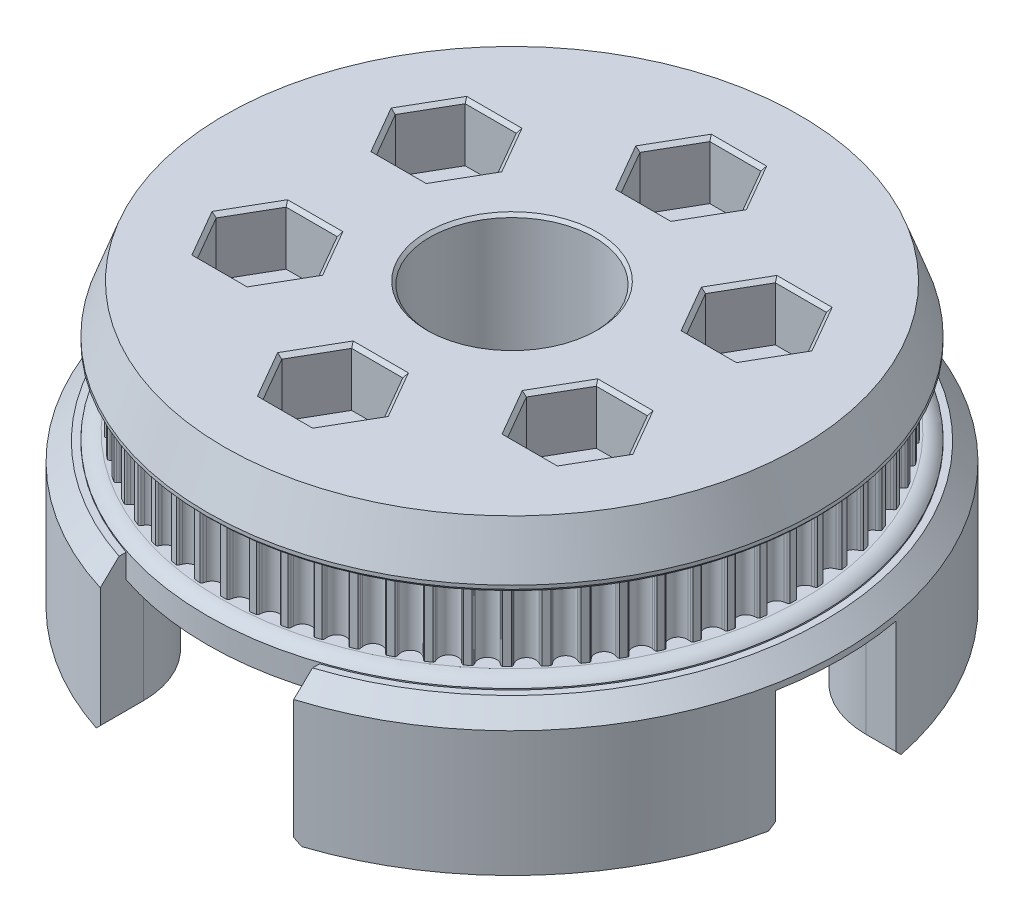
SolidWorks part; units mm, degrees
other "DetailItem2"
material "Markforged"
ref_plane "Front Plane" through (0, 0, 0) normal (0, 0, 1) x (1, 0, 0)
ref_plane "Top Plane" through (0, 0, 0) normal (0, 1, 0) x (1, 0, 0)
ref_plane "Right Plane" through (0, 0, 0) normal (1, 0, 0) x (0, 0, -1)
ref_axis "Centerline" through (0, 10.668, 0) along (0, -1, 0)
sketch "Sketch1" plane through (0, 0, 0) normal (0, 1, 0) x (1, 0, 0)
  circle A0 centre (0, 0) radius 30.6542
  dimension "OuterDiameter" = 61.3084
extrude "ToothOD" add sketch "Sketch1" along normal mid plane 7.62
sketch "Sketch2" plane through (0, 3.81, 0) normal (0, 1, 0) x (1, 0, 0)
  line L0 (0, 29.4858) -> (50000, 29.4858) construction
  line L1 (0, 30.6542) -> (50000, 30.6542) construction
  line L2 (0, 0) -> (0, 50000) construction
  arc A0 (-0.937, 30.2043) -> (0, 29.4858) centre (0, 30.4561) ccw
  arc A1 (-1.1481, 30.6327) -> (1.1481, 30.6327) centre (0, 0) cw
  circle A2 centre (0, 0) radius 30.6542 construction
  arc A3 (-0.937, 30.2043) -> (-1.0078, 30.4561) centre (-11.9754, 27.2378) ccw
  arc A4 (-1.0078, 30.4561) -> (-1.1481, 30.6327) centre (-1.2954, 30.3717) ccw
  circle A5 centre (0, 0) radius 30.6542 construction
  arc A6 (0.937, 30.2043) -> (1.0078, 30.4561) centre (11.9754, 27.2378) cw
  arc A7 (1.0078, 30.4561) -> (1.1481, 30.6327) centre (1.2954, 30.3717) cw
  arc A8 (0, 29.4858) -> (0.937, 30.2043) centre (0, 30.4561) ccw
  dimension "D1" = 1.9406
  dimension "D3" = 22.86
  dimension "D4" = 0.5994
  dimension "D2" = 1.1684
  dimension "D5" = 1.2954
extrude "ToothProfile" cut sketch "Sketch2" against normal through all
pattern_circular "ToothPattern" count 65 over 360 about axis through (0, 3.81, 0) along (0, -1, 0) of "ToothProfile"
sketch "Sketch4" plane through (0, 0, 0) normal (0, 0, 1) x (1, 0, 0)
  line L0 (0, -3.81) -> (30.9082, -3.81)
  line L1 (0, -5.08) -> (32.4322, -5.08)
  line L2 (0, -5.08) -> (0, -3.81)
  line L3 (32.4322, -5.08) -> (32.4322, -4.572)
  line L4 (0, 0) -> (50000, 0) construction
  line L5 (32.4322, 5.08) -> (32.4322, 4.572)
  line L6 (0, 5.08) -> (0, 3.81)
  line L7 (0, 5.08) -> (32.4322, 5.08)
  line L8 (0, 3.81) -> (30.9082, 3.81)
  line L9 (6.7226, -3.81) -> (6.8405, -3.81) construction
  arc A2 (30.9082, -3.81) -> (32.4322, -4.572) centre (30.9082, -5.715) cw
  arc A3 (30.9082, 3.81) -> (32.4322, 4.572) centre (30.9082, 5.715) ccw
  dimension "FlangeID" = 30.9082
  dimension "FlangeOD" = 32.4322
  dimension "D1" = 1.27
  dimension "D2" = 0.508
  dimension "D3" = 1.27
revolve "Flange" add sketch "Sketch4" angle 360 about axis through (0, 10.668, 0) along (0, -1, 0)
sketch "Sketch11" plane through (0, 5.08, 0) normal (0, 1, 0) x (1, 0, 0)
  line L0 (-3.175, 8.636) -> (3.175, 8.636) construction
  text T0 "65" font "Century Gothic" height 1.524
  point P2 (0, 8.636)
  dimension "D1" = 6.35
  dimension "D2" = 8.636
extrude "Small Tooth Count" [suppressed] cut sketch "Sketch11" against normal blind 0.4
sketch "Sketch14" plane through (0, 5.08, 0) normal (0, 1, 0) x (1, 0, 0)
  circle A0 centre (0, 0) radius 32.4322 construction
  circle A1 centre (0, 0) radius 32.4322
extrude "Boss-Extrude2" add sketch "Sketch14" along normal blind 5.842
sketch "Sketch13" plane through (0, -5.08, 0) normal (0, -1, 0) x (1, 0, 0)
  circle A0 centre (0, 0) radius 32.4322 construction
  circle A1 centre (0, 0) radius 32.4322
extrude "Boss-Extrude1" add sketch "Sketch13" along normal offset from surface (2.159 mm away) 18.161 up to face at (0, 10.922, 32.4322)
sketch "Sketch15" plane through (0, -7.239, 0) normal (0, -1, 0) x (1, 0, 0)
  line L0 (-10.287, 23.3625) -> (-10.287, 30.7575)
  line L1 (-10.287, -30.7575) -> (-10.287, -23.3625)
  arc A0 (-10.287, 23.3625) -> (-10.287, -23.3625) centre (0, 0) ccw
  arc A1 (-10.287, -30.7575) -> (-10.287, 30.7575) centre (0, 0) cw
  circle A2 centre (0, 0) radius 32.4322 construction
  dimension "D1" = 25.527
  dimension "D2" = 10.287
extrude "Boss-Extrude3" add sketch "Sketch15" along normal blind 12.7
sketch "Sketch20" plane through (0, -19.939, 0) normal (0, -1, 0) x (1, 0, 0)
  line L0 (-10.287, 33.5085) -> (-10.287, 30.7575)
  line L1 (-10.287, -33.5085) -> (-10.287, -30.7575)
  arc A0 (-10.287, -33.5085) -> (-10.287, 33.5085) centre (0, 0) cw
  arc A1 (-10.287, 30.7575) -> (-10.287, -30.7575) centre (0, 0) ccw construction
  arc A2 (-10.287, 30.7575) -> (-10.287, -30.7575) centre (0, 0) ccw
  arc A3 (-10.287, 23.3625) -> (-10.287, -23.3625) centre (0, 0) ccw construction
  dimension "D1" = 9.525
extrude "Boss-Extrude5" add sketch "Sketch20" against normal offset from surface (15.24 mm away) 2.54 up to face at (-3.4172, -7.239, 0) offset beyond the face yes
mirror "Mirror1" about plane through (0, 0, 0) normal (1, 0, 0) of "Boss-Extrude5", "Boss-Extrude3"
sketch "Sketch16" plane through (0, -7.239, 0) normal (0, -1, 0) x (1, 0, 0)
  line L0 (0, 0) -> (0, 19.05) construction
  circle A0 centre (0, 19.05) radius 2.5527
  dimension "D2" = 5.1054
  dimension "D1" = 19.05
extrude "Cut-Extrude1" cut sketch "Sketch16" against normal through all
pattern_circular "CirPattern1" count 6 over 360 about axis through (0, 10.668, 0) along (0, 1, 0) of "Cut-Extrude1"
sketch "Sketch17" plane through (0, -7.239, 0) normal (0, -1, 0) x (1, 0, 0)
  circle A0 centre (0, 0) radius 8.7376
  dimension "D1" = 17.4752
extrude "Cut-Extrude2" cut sketch "Sketch17" against normal through all
sketch "Sketch18" plane through (0, -7.239, 0) normal (0, -1, 0) x (1, 0, 0)
  circle A0 centre (0, 0) radius 12.7
  circle A1 centre (0, 0) radius 8.7376 construction
  circle A2 centre (0, 0) radius 8.7376
  dimension "D1" = 25.4
extrude "Boss-Extrude4" add sketch "Sketch18" along normal offset from surface (8.255 mm away) 15.494 up to plane "Top Plane" offset beyond the face yes
sketch "Sketch19" plane through (0, 10.922, 0) normal (0, 1, 0) x (1, 0, 0)
  line L1 (2.7203, 14.3383) -> (5.4406, 19.05)
  line L2 (5.4406, 19.05) -> (2.7203, 23.7617)
  line L3 (2.7203, 23.7617) -> (-2.7203, 23.7617)
  line L4 (-2.7203, 23.7617) -> (-5.4406, 19.05)
  line L5 (-5.4406, 19.05) -> (-2.7203, 14.3383)
  line L6 (-2.7203, 14.3383) -> (2.7203, 14.3383)
  circle A0 centre (0, 19.05) radius 4.7117 construction
  dimension "D1" = 9.4234
extrude "Cut-Extrude3" cut sketch "Sketch19" against normal blind 6.985
pattern_circular "CirPattern2" count 6 over 360 about axis through (0, 10.668, 0) along (0, 1, 0) of "Cut-Extrude3"
sketch "Sketch22" plane through (0, -7.239, 0) normal (0, -1, 0) x (1, 0, 0)
  line L0 (-34.4603, 6.4135) -> (-24.7082, 6.4135)
  line L1 (-24.7082, 6.4135) -> (-24.7082, -6.4135)
  line L2 (-24.7082, -6.4135) -> (-34.4603, -6.4135)
  line L3 (24.7082, -6.4135) -> (34.4603, -6.4135)
  line L4 (24.7082, -6.4135) -> (24.7082, 6.4135)
  line L5 (24.7082, 6.4135) -> (34.4603, 6.4135)
  arc A0 (10.287, -33.5085) -> (10.287, 33.5085) centre (0, 0) ccw construction
  arc A1 (-10.287, 33.5085) -> (-10.287, -33.5085) centre (0, 0) ccw construction
  arc A2 (34.4603, -6.4135) -> (34.4603, 6.4135) centre (0, 0) ccw
  arc A3 (-34.4603, 6.4135) -> (-34.4603, -6.4135) centre (0, 0) ccw
  arc A4 (-10.287, 23.3625) -> (-10.287, -23.3625) centre (0, 0) ccw construction
  arc A5 (-10.287, 23.3625) -> (-10.287, -23.3625) centre (0, 0) ccw construction
  arc A6 (10.287, -23.3625) -> (10.287, 23.3625) centre (0, 0) ccw construction
  dimension "D1" = 12.827
extrude "Cut-Extrude5" cut sketch "Sketch22" along normal through all
sketch "Sketch21" plane through (0, 10.922, 0) normal (0, 1, 0) x (1, 0, 0)
  circle A0 centre (0, 0) radius 35.052
  arc A1 (-10.287, 33.5085) -> (-10.287, -33.5085) centre (0, 0) ccw construction
extrude "Cut-Extrude4" cut sketch "Sketch21" against normal blind 0.889
chamfer "Chamfer6" distance 0.381 angle 45 36 edges at (4.0805, 10.033, -21.4059) (4.0805, 10.033, -16.6942) (0, 10.033, -14.3383) (-4.0805, 10.033, -16.6941) (-4.0805, 10.033, -21.4058) (0, 10.033, -23.7617) (-12.4173, 10.033, -7.1691) (-12.4173, 10.033, -11.8808) (-16.4978, 10.033, -14.2367) (-20.5782, 10.033, -11.8808) (-20.5782, 10.033, -7.1691) (-16.4978, 10.033, -4.8133) (-12.4173, 10.033, 11.8809) (-12.4173, 10.033, 7.1692) (-16.4978, 10.033, 4.8133) (-20.5782, 10.033, 7.1692) (-20.5782, 10.033, 11.8809) (-16.4978, 10.033, 14.2367) (4.0805, 10.033, 21.4058) (0, 10.033, 23.7617) (-4.0805, 10.033, 21.4059) (-4.0805, 10.033, 16.6942) (0, 10.033, 14.3383) (4.0805, 10.033, 16.6941) (20.5782, 10.033, 7.1691) (20.5782, 10.033, 11.8808) (16.4978, 10.033, 14.2367) (12.4173, 10.033, 11.8808) (12.4173, 10.033, 7.1691) (16.4978, 10.033, 4.8133) (12.4173, 10.033, -7.1692) (16.4978, 10.033, -4.8133) (20.5782, 10.033, -7.1692) (20.5782, 10.033, -11.8809) (12.4173, 10.033, -11.8809) (16.4978, 10.033, -14.2367)
fillet "Fillet1" radius 9.525 8 edges at (-10.287, -13.589, -23.3625) (10.287, -13.589, -23.3625) (-10.287, -13.589, 23.3625) (10.287, -13.589, 23.3625) (-24.7082, -13.589, 6.4135) (-24.7082, -13.589, -6.4135) (24.7082, -13.589, 6.4135) (24.7082, -13.589, -6.4135)
chamfer "Chamfer2" distance 0.635 angle 45 20 edges at (-10.287, -19.939, -31.2122) (-32.8395, -19.939, -6.4135) (-11.3857, -19.939, -24.4748) (-26.2452, -19.939, -7.8151) (-19.1733, -19.939, -16.8527) (10.287, -19.939, -31.2122) (32.8395, -19.939, -6.4135) (11.3857, -19.939, -24.4748) (26.2452, -19.939, -7.8151) (19.1733, -19.939, -16.8527) (32.8395, -19.939, 6.4135) (10.287, -19.939, 31.2122) (26.2452, -19.939, 7.8151) (11.3857, -19.939, 24.4748) (19.1733, -19.939, 16.8527) (-32.8395, -19.939, 6.4135) (-10.287, -19.939, 31.2122) (-26.2452, -19.939, 7.8151) (-11.3857, -19.939, 24.4748) (-19.1733, -19.939, 16.8527)
chamfer "Chamfer3" distance 5.08 angle 20 1 edges at (0, 10.033, 32.4322) first distance on face at (0, 4.572, 32.4322)
chamfer "Chamfer4" distance 0.3175 angle 45 1 edges at (0, 10.033, 8.7376)
chamfer "Chamfer5" distance 1.905 angle 45 2 edges at (35.052, -4.699, 0) (-35.052, -4.699, 0)
equation "\"OuterDiameter@Sketch1\"= \"OD\""
equation "\"Teeth\"= \"No_Teeth\""
equation "\"PD\"= \"No_Teeth\" * 3mm / pi"
equation "\"OD\"= \"PD\" - .030"
equation "\"ToothCount@ToothPattern\" = \"Teeth\""
equation "\"Angle\"= 360 / \"Teeth\""
equation "\"AngleSpacing@ToothPattern\" = \"Angle\""
equation "\"FlangeID@Sketch4\"=\"OD\"/2+.01"
equation "\"FlangeOD@Sketch4\"=\"PD\"/2+.055"
equation "\"Bearing_Feature\"= \"Bearing_Boss\""
equation "\"TopBearingBoss\" = IIF ( \"Bearing_Feature\" > 0 , \"unsuppressed\" , \"suppressed\" )"
equation "\"HexBore\"= \"Hex_Bore\""
equation "\"Large Tooth Count\"= iif ( \"No_Teeth\" < 27 , \"suppressed\" , \"unsuppressed\" )"
equation "\"Small Tooth Count\"= iif ( \"No_Teeth\" < 27 , \"unsuppressed\" , \"suppressed\" )"
equation "\"D2@Sketch11\"=\"HexBore\"/2+.09"
equation "\"BottomBearingBoss\" = iif ( \"Bearing_Feature\" > 1 , \"unsuppressed\" , \"suppressed\" )"
